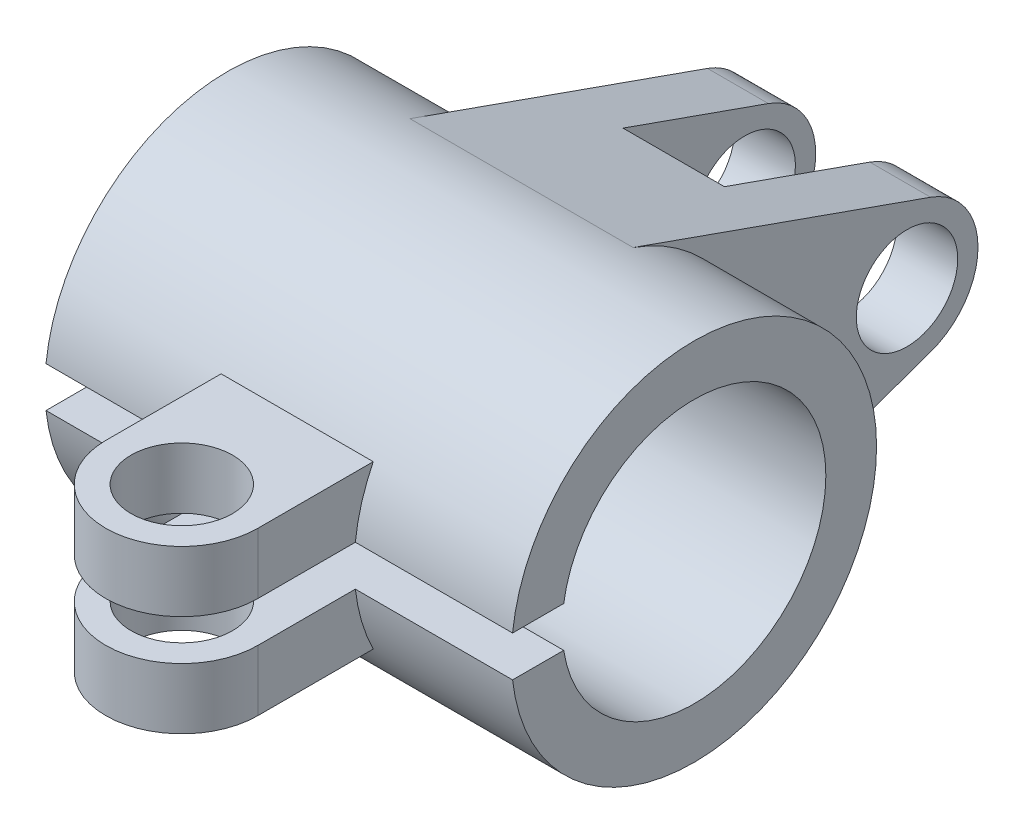
SolidWorks part; units mm, degrees
ref_plane "Front Plane" through (0, 0, 0) normal (0, 0, 1) x (1, 0, 0)
ref_plane "Top Plane" through (0, 0, 0) normal (0, 1, 0) x (1, 0, 0)
ref_plane "Right Plane" through (0, 0, 0) normal (1, 0, 0) x (0, 0, -1)
sketch "Sketch1" plane through (0, 0, 0) normal (1, 0, 0) x (0, 0, -1)
  line L0 (0, 0) -> (33644.4846, 0) construction
  line L1 (0, 0) -> (0, 33644.4846) construction
  line L2 (6, 16.9706) -> (35.3333, 6.5997)
  line L3 (6, -16.9706) -> (35.3333, -6.5997)
  line L4 (21, 11.6673) -> (21, -11.6673)
  line L5 (-12.8452, 2) -> (-35, 2)
  line L6 (-35, 8) -> (-35, 2)
  line L7 (-35, 8) -> (-16.1245, 8)
  line L8 (-12.8452, -2) -> (-35, -2)
  line L9 (-35, -2) -> (-35, -8)
  line L10 (-35, -8) -> (-16.1245, -8)
  circle A0 centre (0, 0) radius 13
  circle A1 centre (0, 0) radius 18
  circle A2 centre (33, 0) radius 5
  arc A3 (35.3333, -6.5997) -> (35.3333, 6.5997) centre (33, 0) ccw
  dimension "D1" = 26
  dimension "D2" = 36
  dimension "D3" = 10
  dimension "D4" = 14
  dimension "D5" = 33
  dimension "D6" = 12
  dimension "D7" = 6
  dimension "D8" = 4
  dimension "D9" = 35
extrude "Boss-Extrude1" add sketch "Sketch1" along normal mid plane 46 contours A1 L5 A0 L8 region at (0, 10.0988, -14.2819)
extrude "Boss-Extrude2" add sketch "Sketch1<3>" along normal mid plane 22 contours A1 L3 L4 L2 region at (0, 13.9691, -13.3763)
sketch "Sketch1<3>" plane through (0, 0, 0) normal (1, 0, 0) x (0, 0, -1) same geometry as "Sketch1"
extrude "Boss-Extrude3" add sketch "Sketch1<4>" along normal blind 6 from offset 5 contours L3 A3 L2 L4 A2 region at (0, 0, -27.5339)
sketch "Sketch1<4>" plane through (0, 0, 0) normal (1, 0, 0) x (0, 0, -1) same geometry as "Sketch1"
extrude "Boss-Extrude4" add sketch "Sketch1<5>" against normal blind 6 from offset 5 contours L3 A3 L2 L4 A2 region at (0, 0, -27.5339) offset against normal yes
sketch "Sketch1<5>" plane through (0, 0, 0) normal (1, 0, 0) x (0, 0, -1) same geometry as "Sketch1"
extrude "Boss-Extrude5" add sketch "Sketch1<7>" along normal mid plane 15 contours A1 L8 L9 L10 | A1 L7 L6 L5 region at (0, 5.0492, 26.0911) region at (0, -5.0492, 26.0911)
sketch "Sketch1<7>" plane through (0, 0, 0) normal (1, 0, 0) x (0, 0, -1) same geometry as "Sketch1"
fillet "Fillet1" 2 edges at (7.5, -5, 35) (-7.5, -5, 35) type full round first side face at (7.5, -5.0193, 26.0689) second side face at (-7.5, -5.0193, 26.0689) middle face at (0, -5, 35)
fillet "Fillet2" 2 edges at (7.5, 5, 35) (-7.5, 5, 35) type full round first side face at (7.5, 5.0193, 26.0689) second side face at (-7.5, 5.0193, 26.0689) middle face at (0, 5, 35)
hole_wizard "Ø10.0mm Dowel Hole1" positions "3DSketch1" profile "Sketch2" hole size "Ø10.0" standard "ISO" end condition through all
sketch3d "3DSketch1"
  line L0 (0, -2, 27.5) -> (0, -8, 27.5) construction
  point P0 (0, -8, 27.5)
sketch "Sketch2" plane through (0, -8, 27.5) normal (1, 0, 0) x (0, 0, -1)
  line L0 (0, 0) -> (0, 26)
  line L1 (0, 26) -> (5, 26)
  line L2 (5, 26) -> (5, 0)
  line L5 (5, 0) -> (0, 0)
  line L11 (0, -6.35) -> (0, 107.95) construction
  dimension "Thru Hole Dia." = 10
  dimension "Thru Hole Depth" = 26
